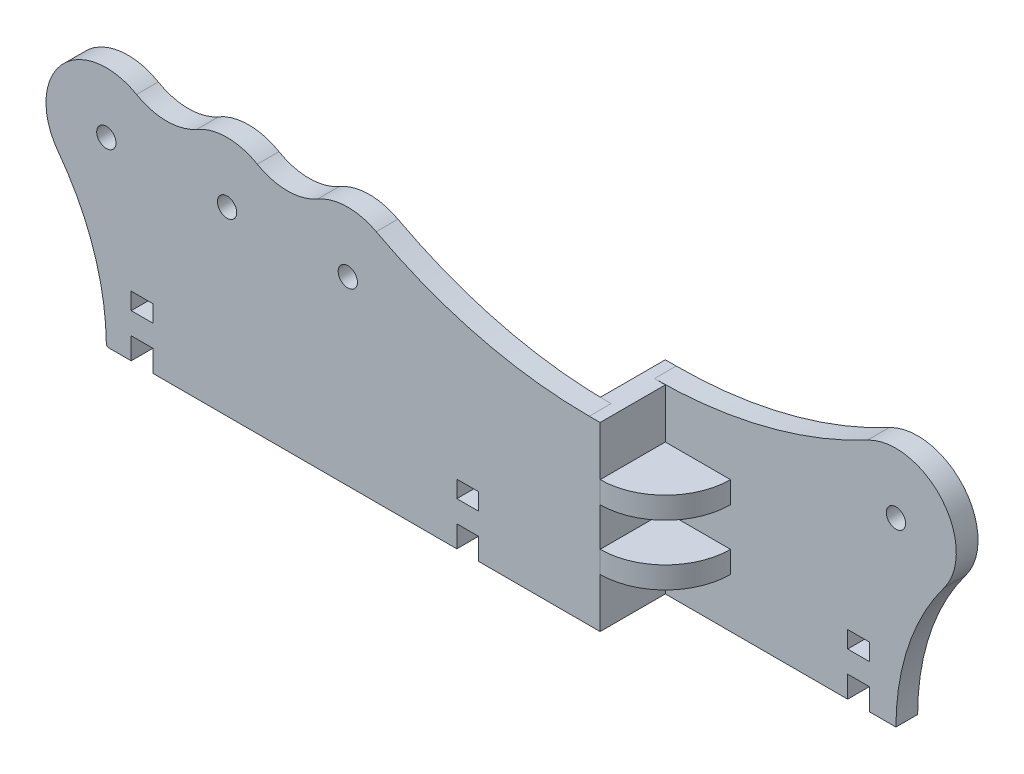
SolidWorks part; units mm, degrees
ref_plane "Front Plane" through (0, 0, 0) normal (0, 0, 1) x (1, 0, 0)
ref_plane "Top Plane" through (0, 0, 0) normal (0, 1, 0) x (1, 0, 0)
ref_plane "Right Plane" through (0, 0, 0) normal (1, 0, 0) x (0, 0, -1)
sketch "Sketch1" plane through (0, 0, 0) normal (0, 0, 1) x (1, 0, 0)
  line L0 (-125, 0) -> (125, 0) construction
  circle A0 centre (-125, 0) radius 4
  circle A1 centre (125, 0) radius 4
  circle A2 centre (-125, 0) radius 8
  circle A3 centre (125, 0) radius 8
  dimension "D1" = 8
  dimension "D3" = 16
  dimension "D2" = 250
extrude "Boss-Extrude1" add sketch "Sketch1" along normal blind 9
sketch "Sketch2" plane through (0, 0, 0) normal (0, 0, 1) x (1, 0, 0)
  line L0 (-125, -25) -> (125, -25) construction
  line L1 (0, -25) -> (0, -75) construction
  line L2 (-125, -75) -> (125, -75)
  line L3 (-125, -75) -> (-125, -25) construction
  line L4 (-175, 0) -> (-125, 0) construction
  line L5 (-175, 0) -> (-175, -75) construction
  line L6 (-125, 0) -> (125, 0) construction
  line L7 (-175, -75) -> (-125, -75)
  line L8 (-275, -75) -> (-175, -75) construction
  line L9 (225, -75) -> (125, -75) construction
  circle A0 centre (-125, 0) radius 25
  circle A1 centre (-125, 0) radius 4
  circle A2 centre (-125, 0) radius 4 construction
  circle A3 centre (125, 0) radius 4
  circle A4 centre (125, 0) radius 25
  circle A5 centre (125, 0) radius 4 construction
  circle A9 centre (-75, 0) radius 4
  circle A10 centre (-175, 0) radius 4
  circle A13 centre (-175, 0) radius 25
  circle A14 centre (-75, 0) radius 25
  circle A15 centre (-275, -75) radius 100
  circle A16 centre (225, -75) radius 100
  circle A17 centre (25, 187.5) radius 187.5
  circle A18 centre (-150, 43.3013) radius 25
  circle A19 centre (-100, 43.3013) radius 25
  dimension "D2" = 50
  dimension "D3" = 50
  dimension "D1" = 50
  dimension "D4" = 50
extrude "Boss-Extrude3" add sketch "Sketch2" along normal blind 9 contours A17 A14 A0 A13 A15 L7 L2 A16 A4 | A4 A3 | A14 A9 | A19 A0 A14 | A0 A1 | A18 A13 A0 | A13 A10 region at (-15.9174, -39.5028, 0) region at (106.5555, -15.8096, 0) region at (-193.176, 16.1176, 0) region at (-150, 14.4338, 0) region at (-146.0383, 12.1464, 0) region at (-54.169, 12.4986, 0) region at (-100, 14.4338, 0)
fillet "Fillet1" radius 1 2 edges at (125, -75, 4.5) (-175, -75, 4.5)
sketch "Sketch3" plane through (0, 0, 0) normal (0, 0, 1) x (1, 0, 0)
  line L0 (25, 0) -> (25, -75)
  line L1 (-174.005, -75) -> (124.005, -75) construction
  line L2 (25, -75) -> (150, -75)
  line L3 (150, -75) -> (150, 25)
  line L4 (150, 25) -> (25, 25)
  line L5 (25, 25) -> (25, 0)
  arc A0 (-63.2353, 22.0588) -> (113.2353, 22.0588) centre (25, 187.5) ccw construction
  arc A1 (145, -15) -> (113.2353, 22.0588) centre (125, 0) ccw construction
extrude "Cut-Extrude1" cut sketch "Sketch3" along normal through all
sketch "Sketch4" plane through (0, -75, 0) normal (0, -1, 0) x (1, 0, 0)
  line L0 (25, 9) -> (-63.2353, 9) construction
  line L1 (20.5, 9) -> (29.5, 9)
  line L2 (20.5, 9) -> (20.5, -18)
  line L3 (20.5, -18) -> (29.5, -18)
  line L4 (29.5, 9) -> (29.5, -18)
  line L5 (25, -18) -> (25, 9) construction
  point P8 (32.7112, 9)
  point P9 (28.2112, 9)
  point P10 (29.2644, 9)
  point P11 (0, 0)
  dimension "D1" = 9
  dimension "D2" = 27
extrude "Boss-Extrude4" add sketch "Sketch4" against normal up to vertex (75 mm away) up to point (25, 0, 0)
sketch "Sketch5" plane through (0, 0, -18) normal (0, 0, -1) x (-1, 0, 0)
  line L0 (-125, -75) -> (-20.5, -75)
  line L1 (-20.5, -75) -> (-20.5, 0)
  line L2 (-20.5, 0) -> (-100, 0)
  circle A0 centre (-125, 0) radius 4
  circle A1 centre (-125, 0) radius 25
  circle A2 centre (-225, -75) radius 100
  circle A3 centre (-225, -75) radius 100 construction
  circle A4 centre (-125, 0) radius 25 construction
  circle A5 centre (-125, 0) radius 4 construction
  circle A6 centre (-25, 187.5) radius 187.5
  circle A7 centre (-25, 187.5) radius 187.5 construction
  line M4 (-29.5, -75) -> (-20.5, -75)
  line M5 (-20.5, -75) -> (-20.5, 0)
  line M6 (-20.5, 0) -> (-29.5, 0)
  line M7 (-29.5, 0) -> (-29.5, -75)
extrude "Boss-Extrude5" add sketch "Sketch5" along normal blind 9 contours A2 L0 L2 A1 M7 | A1 A0 | L2 M7 M4 M5 M6 | A6 A1 L2 region at (76.4581, -39.349, -18) region at (25, -37.5, -18) region at (143.4445, 15.8096, -18) region at (83.4345, 5.5048, -18)
sketch "Sketch6" plane through (0, 0, 0) normal (0, 0, -1) x (-1, 0, 0)
  line L0 (-20.5, 0) -> (-20.5, -25) construction
  line L1 (-20.5, 0) -> (-20.5, -75) construction
  line L2 (-20.5, -25) -> (-20.5, -50) construction
  line L3 (-20.5, -75) -> (-20.5, 0) construction
  line L4 (-20.5, -50) -> (-20.5, -75) construction
ref_plane "Plane1" through (0, -25, 0) normal (0, 1, 0) x (1, 0, 0)
ref_plane "Plane2" through (0, -50, 0) normal (0, 1, 0) x (1, 0, 0)
sketch "Sketch7" plane through (0, -25, 0) normal (0, 1, 0) x (1, 0, 0)
  line L0 (56.5, 18) -> (29.5, 18)
  line L1 (29.5, 18) -> (29.5, -9)
  line L2 (20.5, 27) -> (20.5, 0)
  line L3 (20.5, 0) -> (-6.5, 0)
  circle A0 centre (20.5, 0) radius 27
  circle A1 centre (29.5, 18) radius 27
extrude "Boss-Extrude6" add sketch "Sketch7" along normal blind 4.5 and the other way blind 4.5 contours L1 A1 A0 L0 | A0 A1 L0 | A1 A0 L3 | A0 A1 L3 L2 region at (49.8154, -25, -11.0447) region at (37.3919, -25, -4.7267) region at (0.1846, -25, -6.9553) region at (12.6081, -25, -13.2733)
extrude "Boss-Extrude7" add sketch "Sketch7<3>" along normal blind 4.5 and the other way blind 4.5 from surface contours A0 A1 L0 | L1 A1 A0 L0 | A0 A1 L3 L2 | A1 A0 L3 region at (49.8154, -25, -11.0447) region at (37.3919, -25, -4.7267) region at (0.1846, -25, -6.9553) region at (12.6081, -25, -13.2733) starting at plane "Plane2"
sketch "Sketch7<3>" plane through (0, -25, 0) normal (0, 1, 0) x (1, 0, 0) same geometry as "Sketch7"
sketch "Sketch9" plane through (0, 0, 9) normal (0, 0, 1) x (1, 0, 0)
  line L0 (-174.005, -75) -> (29.5, -75) construction
  line L1 (-164.7085, -50) -> (-155.7085, -50)
  line L2 (-164.7085, -50) -> (-164.7085, -57)
  line L3 (-164.7085, -57) -> (-155.7085, -57)
  line L4 (-155.7085, -50) -> (-155.7085, -57)
  line L5 (-164.7085, -66) -> (-155.7085, -66)
  line L6 (-164.7085, -66) -> (-164.7085, -75)
  line L7 (-164.7085, -75) -> (-155.7085, -75)
  line L8 (-155.7085, -66) -> (-155.7085, -75)
  line L9 (-155.7085, -75) -> (-155.7085, -66) construction
  line L10 (-20.8518, -75) -> (-20.8518, -66) construction
  line L11 (-29.8518, -50) -> (-20.8518, -50)
  line L12 (-29.8518, -50) -> (-29.8518, -57)
  line L13 (-29.8518, -57) -> (-20.8518, -57)
  line L14 (-20.8518, -50) -> (-20.8518, -57)
  line L15 (-29.8518, -66) -> (-20.8518, -66)
  line L16 (-29.8518, -66) -> (-29.8518, -75)
  line L17 (-29.8518, -75) -> (-20.8518, -75)
  line L18 (-20.8518, -66) -> (-20.8518, -75)
  line L19 (125, -75) -> (29.5, -75) construction
  line L20 (105.005, -50) -> (114.005, -50)
  line L21 (105.005, -50) -> (105.005, -57)
  line L22 (105.005, -57) -> (114.005, -57)
  line L23 (114.005, -50) -> (114.005, -57)
  line L24 (105.005, -66) -> (114.005, -66)
  line L25 (105.005, -66) -> (105.005, -75)
  line L26 (105.005, -75) -> (114.005, -75)
  line L27 (114.005, -66) -> (114.005, -75)
extrude "Cut-Extrude2" cut sketch "Sketch9" against normal through all
